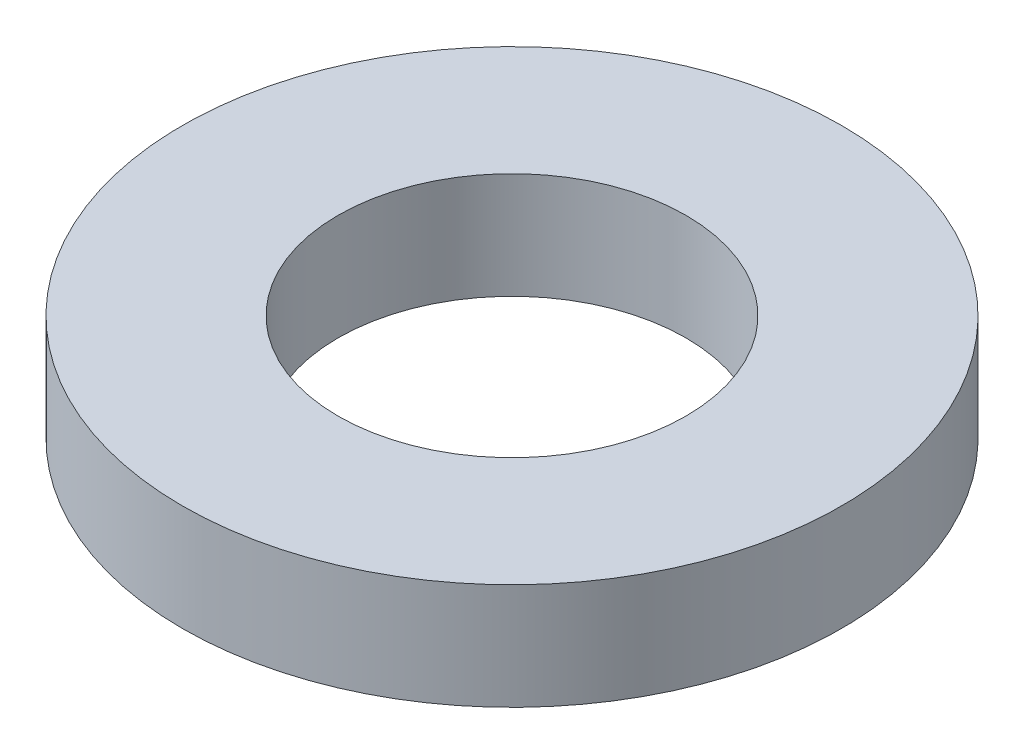
SolidWorks part; units mm, degrees
ref_plane "Front Plane" through (0, 0, 0) normal (0, 0, 1) x (1, 0, 0)
ref_plane "Top Plane" through (0, 0, 0) normal (0, 1, 0) x (1, 0, 0)
ref_plane "Right Plane" through (0, 0, 0) normal (1, 0, 0) x (0, 0, -1)
sketch "Sketch1" plane through (0, 0, 0) normal (0, 1, 0) x (1, 0, 0)
  circle A0 centre (0, 0) radius 90
  dimension "FLANGE_OD" = 180
extrude "Boss-Extrude1" add sketch "Sketch1" along normal blind 29
sketch "Sketch2" plane through (0, 0, 0) normal (0, 1, 0) x (1, 0, 0)
  circle A0 centre (0, 0) radius 47.5
  dimension "BORE_D" = 95
extrude "Cut-Extrude1" cut sketch "Sketch2" along normal through all
sketch "Sketch3" plane through (0, 29, 0) normal (0, 1, 0) x (1, 0, 0)
  circle A0 centre (0, 0) radius 33.2589 construction
  circle A1 centre (-33.2589, 0) radius 5.4689
  dimension "BOLT_D" = 10.9379
  dimension "BOLT_PCD" = 66.5178
extrude "Cut-Extrude2" cut sketch "Sketch3" against normal blind 25.3526 rebuild error yes
pattern_circular "CirPattern1" count 4 over 360 rebuild error yes
